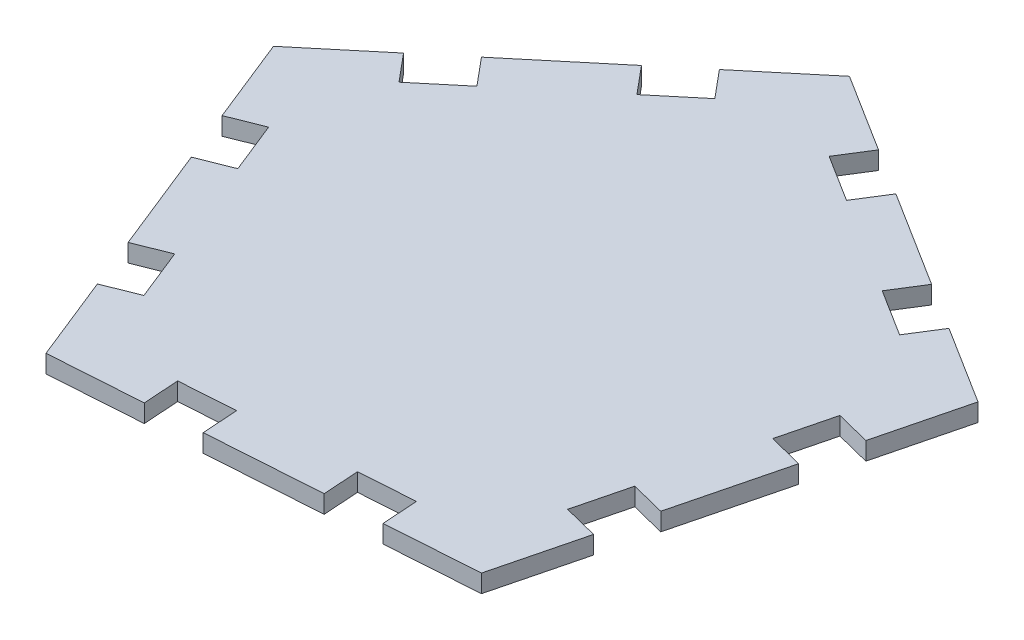
SolidWorks part; units mm, degrees
ref_plane "Front Plane" through (0, 0, 0) normal (0, 0, 1) x (1, 0, 0)
ref_plane "Top Plane" through (0, 0, 0) normal (0, 1, 0) x (1, 0, 0)
ref_plane "Right Plane" through (0, 0, 0) normal (1, 0, 0) x (0, 0, -1)
sketch "Sketch1" plane through (0, 0, 0) normal (0, 1, 0) x (1, 0, 0)
  line L1 (-59.9258, 15.1181) -> (-32.8962, -52.3211)
  line L2 (-32.8962, -52.3211) -> (39.5948, -47.4543)
  line L3 (39.5948, -47.4543) -> (57.3672, 22.9927)
  line L4 (57.3672, 22.9927) -> (-4.14, 61.6646)
  line L5 (-4.14, 61.6646) -> (-59.9258, 15.1181)
  circle A0 centre (0, 0) radius 50 construction
  dimension "D1" = 100
extrude "Boss-Extrude1" add sketch "Sketch1" along normal blind 3.18
ref_axis "Axis" through (0, 3.339, 0) along (0, -1, 0)
sketch "Axis Check" [suppressed] plane through (0, 3.18, 0) normal (0, 1, 0) x (1, 0, 0)
  line L0 (3.3493, -49.8877) -> (-4.14, 61.6646) construction
  line L1 (-32.8962, -52.3211) -> (39.5948, -47.4543) construction
  line L2 (57.3672, 22.9927) -> (-46.411, -18.6015) construction
  line L3 (-59.9258, 15.1181) -> (-32.8962, -52.3211) construction
  line L4 (-32.0329, 38.3913) -> (39.5948, -47.4543) construction
  line L5 (-4.14, 61.6646) -> (-59.9258, 15.1181) construction
  line L6 (-59.9258, 15.1181) -> (48.481, -12.2308) construction
  line L7 (39.5948, -47.4543) -> (57.3672, 22.9927) construction
  line L8 (-32.8962, -52.3211) -> (26.6136, 42.3287) construction
  line L9 (57.3672, 22.9927) -> (-4.14, 61.6646) construction
sketch "Sketch2" plane through (0, 0, 0) normal (0, -1, 0) x (1, 0, 0)
  line L0 (-53.8219, 0.1114) -> (-47.9184, -2.2547)
  line L1 (-53.8219, 0.1114) -> (-50.1648, 9.2358)
  line L2 (-47.9184, -2.2547) -> (-44.2613, 6.8697)
  line L3 (-50.1648, 9.2358) -> (-44.2613, 6.8697)
  line L4 (-59.9258, -15.1181) -> (-32.8962, 52.3211) construction
  line L5 (-42.6572, 27.9673) -> (-39.0002, 37.0917)
  line L6 (-42.6572, 27.9673) -> (-36.7538, 25.6012)
  line L7 (-39.0002, 37.0917) -> (-33.0967, 34.7256)
  line L8 (-36.7538, 25.6012) -> (-33.0967, 34.7256)
  line L9 (-46.411, 18.6015) -> (-19.2439, 7.7129) construction
  line L10 (-40.8287, 32.5295) -> (-34.9252, 30.1634) construction
  dimension "D1" = 6.36
  dimension "D3" = 10.09
  dimension "D2" = 9.83
extrude "Cut F" cut sketch "Sketch2" against normal through all
sketch "Sketch4" [suppressed] plane through (0, 3.18, 0) normal (0, 1, 0) x (1, 0, 0)
  line L9 (26.6136, 42.3287) -> (-26.6136, -42.3287) construction
  line L10 (57.3672, 22.9927) -> (-4.14, 61.6646) construction
  line L11 (-34.4964, -17.2915) -> (0.6335, 38.5824)
  line L12 (-34.4964, -17.2915) -> (-0.6335, -38.5824)
  line L13 (0.6335, 38.5824) -> (34.4964, 17.2915)
  line L14 (-0.6335, -38.5824) -> (34.4964, 17.2915)
  line L15 (-34.4964, -17.2915) -> (34.4964, 17.2915) construction
  line L16 (0.6335, 38.5824) -> (-0.6335, -38.5824) construction
  line L20 (0, 0) -> (39.0006, -24.5211) construction
  circle A0 centre (-21.8232, -34.7095) radius 3.25
  circle A1 centre (23.7041, -14.9036) radius 3.25
  point P5 (0, 0)
  point P6 (-21.8232, -34.7095)
  dimension "D3" = 6.5
  dimension "D1" = 40
  dimension "D2" = 66
  dimension "D4" = 8
  dimension "D5" = 8
extrude "Top Cut" [suppressed] cut sketch "Sketch4" against normal blind 10
sketch "Sketch7" [suppressed] plane through (0, 3.18, 0) normal (0, 1, 0) x (1, 0, 0)
  line L0 (0, 0) -> (26.6136, 42.3287) construction
  line L1 (57.3672, 22.9927) -> (-4.14, 61.6646) construction
  line L2 (-7.1857, -11.4287) -> (-30.8897, 3.4749) construction
  line L3 (-14.3588, -11.6437) -> (-33.0188, 0.0886) construction
  line L5 (0.6335, 38.5824) -> (-34.4964, -17.2915) construction
  circle A0 centre (-30.8897, 3.4749) radius 1
  circle A1 centre (-33.0188, 0.0886) radius 1
  dimension "D5" = 2
  dimension "D1" = 4
  dimension "D2" = 17.5
  dimension "D3" = 8
  dimension "D4" = 8
extrude "Top Cut 2" [suppressed] cut sketch "Sketch7" against normal through all
sketch "Sketch10" [suppressed] plane through (0, 3.18, 0) normal (0, 1, 0) x (1, 0, 0)
  line L0 (26.6136, 42.3287) -> (17.565, 27.9369) construction
  line L1 (57.3672, 22.9927) -> (-4.14, 61.6646) construction
  line L2 (34.4964, 17.2915) -> (0.6335, 38.5824) construction
  line L3 (33.0578, 31.7802) -> (13.6147, 44.0048) construction
  line L4 (34.4964, 17.2915) -> (0.6335, 38.5824) construction
  circle A0 centre (19.4532, 40.3339) radius 1
  circle A1 centre (27.919, 35.0111) radius 1
  dimension "D1" = 11.5
  dimension "D2" = 2
  dimension "D3" = 5
extrude "Top Cut 3" [suppressed] cut sketch "Sketch10" against normal blind 10
sketch "Sketch8" [suppressed] plane through (0, 3.18, 0) normal (0, 1, 0) x (1, 0, 0)
  line L0 (3.3493, -49.8877) -> (-4.14, 61.6646) construction
  line L5 (-32.8962, -52.3211) -> (39.5948, -47.4543) construction
  line L6 (-17.9455, -31.2723) -> (21.9647, -28.5929)
  line L11 (-17.9455, -31.2723) -> (-21.9647, 28.5929)
  line L12 (21.9647, -28.5929) -> (17.9455, 31.2723)
  line L13 (-21.9647, 28.5929) -> (17.9455, 31.2723)
  point P4 (1.4955, -22.2759)
  dimension "D1" = 60
  dimension "D2" = 40
  dimension "D3" = 20
extrude "Bottom Cut" [suppressed] cut sketch "Sketch8" against normal blind 10
sketch "Sketch9" [suppressed] plane through (0, 3.18, 0) normal (0, 1, 0) x (1, 0, 0)
  line L0 (19.9551, 1.3397) -> (-19.9551, -1.3397) construction
  line L1 (21.9647, -28.5929) -> (17.9455, 31.2723) construction
  line L2 (-21.9647, 28.5929) -> (-17.9455, -31.2723) construction
  line L3 (-19.9551, -1.3397) -> (-44.4689, -2.9855) construction
  line L4 (19.9551, 1.3397) -> (42.6839, 2.8657) construction
  line L5 (-32.8962, -52.3211) -> (39.5948, -47.4543) construction
  line L6 (-29.6051, -6.8886) -> (-32.3788, -7.0748)
  line L7 (-29.6051, -6.8886) -> (-30.2602, 2.8694)
  line L8 (-30.2602, 2.8694) -> (-33.0339, 2.6832)
  line L9 (-32.3788, -7.0748) -> (-33.0339, 2.6832)
  line L10 (-29.6051, -6.8886) -> (-33.0339, 2.6832) construction
  line L11 (-30.2602, 2.8694) -> (-32.3788, -7.0748) construction
  line L12 (33.0339, -2.6832) -> (30.2602, -2.8694)
  line L13 (33.0339, -2.6832) -> (32.3788, 7.0748)
  line L14 (32.3788, 7.0748) -> (29.6051, 6.8886)
  line L15 (30.2602, -2.8694) -> (29.6051, 6.8886)
  line L16 (33.0339, -2.6832) -> (29.6051, 6.8886) construction
  line L17 (32.3788, 7.0748) -> (30.2602, -2.8694) construction
  line L18 (-32.8962, -52.3211) -> (39.5948, -47.4543) construction
  point P6 (-31.3195, -2.1027)
  point P13 (31.3195, 2.1027)
  dimension "D1" = 9.83
  dimension "D4" = 9.83
  dimension "D5" = 10
  dimension "D6" = 10
  dimension "D2" = 2.78
  dimension "D3" = 2.78
extrude "Battery Holder Cut" [suppressed] cut sketch "Sketch9" against normal blind 6.36
sketch "Sketch3" [suppressed] plane through (0, 3.18, 0) normal (0, 1, 0) x (1, 0, 0)
  line L0 (0, 0) -> (-40.9819, 49.1167) construction
  line L1 (-51.5331, 30.4039) -> (-43.3839, 20.6371)
  line L3 (-43.3839, 20.6371) -> (-35.5751, 27.1526)
  line L4 (-43.7243, 36.9194) -> (-35.5751, 27.1526)
  line L5 (-4.14, 61.6646) -> (-59.9258, 15.1181) construction
  line L6 (-71.9961, 5.0469) -> (-69.9588, 2.6052)
  line L7 (-71.9961, 5.0469) -> (-47.4739, 25.5077)
  line L14 (-28.4906, 49.63) -> (-20.3415, 39.8633)
  line L16 (-20.3415, 39.8633) -> (-12.5327, 46.3788)
  line L17 (-20.6818, 56.1455) -> (-12.5327, 46.3788)
  line L18 (-40.5056, 25.1246) -> (-39.4795, 23.8949) construction
  line L19 (-51.5331, 30.4039) -> (-43.7243, 36.9194)
  line L21 (-28.4906, 49.63) -> (-20.6818, 56.1455)
  line L22 (-16.6073, 51.2621) -> (4.7866, 69.1127)
  line L23 (-39.6497, 32.036) -> (-24.4161, 44.7466)
  line M18 (-4.14, 61.6646) -> (-59.9258, 15.1181)
  dimension "D1" = 12.72
  dimension "D2" = 10.17
  dimension "D3" = 9.92
  dimension "D4" = 100
extrude "Extrude M" [suppressed] add sketch "Sketch3" against normal up to surface (3.18 mm away) contours L21 L14 L7 L17 | L19 L1 L4 M18 up to face at (-26.7442, 0, 10.7191)
pattern_circular "Circle F" count 5 over 360 about axis through (0, 3.339, 0) along (0, -1, 0) of "Cut F"
pattern_circular "Circle M" [suppressed] count 5 over 360 about axis through (0, 3.339, 0) along (0, -1, 0) of bodies 173
pattern_circular "Circle Side F" [suppressed] count 5 over 360 about axis through (0, 3.339, 0) along (0, -1, 0) of bodies 173
pattern_circular "Circle Side M" [suppressed] count 5 over 360 about axis through (0, 3.339, 0) along (0, -1, 0) of bodies 168
equation "\"kerf\"= .17mm"
equation "\"tabWidthF\"= 10 - \"kerf\""
equation "\"tabThickness\"= 6.36mm"
equation "\"D1@Sketch2\"=\"tabThickness\""
equation "\"tabWidthM\"= 10 + \"kerf\""
equation "\"halfkerf\"= \"kerf\" / 2.00mm"
equation "\"D1@Sketch9\"=\"tabWidthF\""
equation "\"D4@Sketch9\"=\"tabWidthF\""
equation "\"D1@Battery Holder Cut\" = \"tabThickness\""
equation "\"tabLength\" = \"kerf\" + 12"
